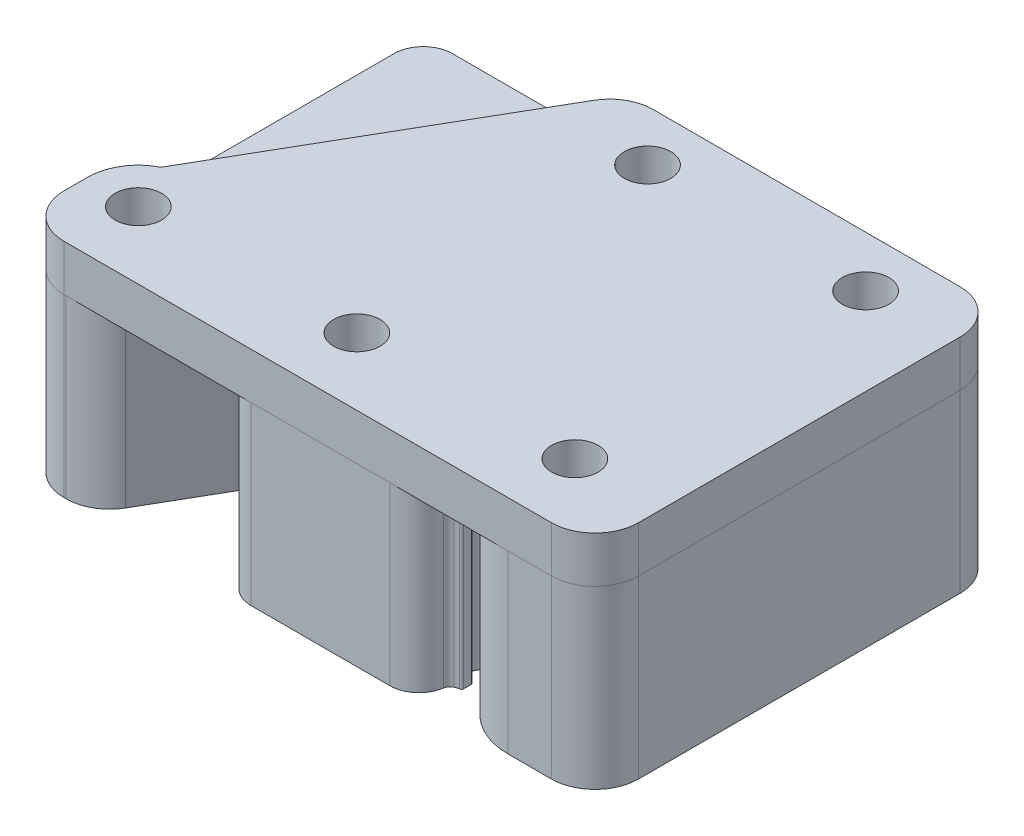
SolidWorks part; units mm, degrees
material "AISI 1045 Steel, cold drawn"
ref_plane "Front Plane" through (0, 0, 0) normal (0, 0, 1) x (1, 0, 0)
ref_plane "Top Plane" through (0, 0, 0) normal (0, 1, 0) x (1, 0, 0)
ref_plane "Right Plane" through (0, 0, 0) normal (1, 0, 0) x (0, 0, -1)
sketch "Sketch1" plane through (0, 0, 0) normal (0, 1, 0) x (1, 0, 0)
  line L0 (-13.5, -13.5) -> (-13.5, -14.619)
  line L1 (7.5, -10) -> (-7.5, -10) construction
  line L2 (7.5, -10) -> (7.5, 10) construction
  line L3 (7.5, 10) -> (-7.5, 10) construction
  line L4 (-7.5, -10) -> (-7.5, 10) construction
  line L5 (7.5, -10) -> (-7.5, 10) construction
  line L6 (7.5, 10) -> (-7.5, -10) construction
  line L7 (13.5, -13.5) -> (-13.5, -13.5) construction
  line L8 (13.5, -13.5) -> (13.5, 13.5)
  line L9 (13.5, 13.5) -> (-13.5, 13.5)
  line L10 (-13.5, -13.5) -> (-13.5, 13.5)
  line L11 (13.5, -13.5) -> (-13.5, 13.5) construction
  line L12 (13.5, 13.5) -> (-13.5, -13.5) construction
  line L13 (-13.5, -14.619) -> (13.5, -14.619)
  line L14 (13.5, -14.619) -> (13.5, -13.5)
  point P0 (0, 0)
  point P6 (0, 0)
  dimension "D1" = 15
  dimension "D2" = 27
  dimension "D3" = 1.119
  dimension "D4" = 20
extrude "Boss-Extrude1" add sketch "Sketch1" along normal mid plane 12.1
hole_wizard "M3 Clearance Hole1" positions "Sketch2" profile "Sketch3" hole size "M3" standard "ANSI Metric" end condition through all
sketch "Sketch2" plane through (0, 6.05, 0) normal (0, 1, 0) x (1, 0, 0)
  point P0 (-7.5, 10)
  point P3 (7.5, 10)
  point P6 (7.5, -10)
  point P9 (-7.5, -10)
sketch "Sketch3" plane through (-7.5, 6.05, -10) normal (1, 0, 0) x (0, 0, 1)
  line L0 (0, 0) -> (0, 12.1)
  line L1 (0, 12.1) -> (1.6, 12.1)
  line L2 (1.6, 12.1) -> (1.6, 0)
  line L5 (1.6, 0) -> (0, 0)
  line L11 (0, -6.35) -> (0, 107.95) construction
  dimension "Thru Hole Dia." = 3.2
  dimension "Thru Hole Depth" = 12.1
sketch "Sketch6" plane through (0, 6.05, 0) normal (0, 1, 0) x (1, 0, 0)
  line L0 (13.5, 13.5) -> (-13.5, 13.5) construction
  line L1 (-13.5, -14.619) -> (-28, -14.619)
  line L2 (-13.5, -14.619) -> (-13.5, 13.5)
  line L3 (-13.5, 13.5) -> (-28, 13.5)
  line L4 (-28, -14.619) -> (-28, 13.5)
  dimension "D1" = 28
extrude "Boss-Extrude3" add sketch "Sketch6" against normal up to surface (12.1 mm away) up to face at (-7.5, -6.05, -8.4)
sketch "Sketch8" plane through (0, 6.05, 0) normal (0, 1, 0) x (1, 0, 0)
  line L0 (-28, -14.619) -> (13.5, -14.619) construction
  line L2 (2.881, -10) -> (2.881, 4)
  line L3 (2.881, 4) -> (1.361, 4)
  line L4 (1.361, -14.619) -> (1.361, 4)
  line L5 (7.5, -14.619) -> (1.361, -14.619)
  arc A0 (2.881, -10) -> (7.5, -14.619) centre (7.5, -10) ccw
  dimension "D1" = 1.52
  dimension "D2" = 14
extrude "Cut-Extrude2" cut sketch "Sketch8" against normal up to surface (12.1 mm away) up to face at (-7.5, -6.05, -8.4)
sketch "Sketch9" plane through (0, 6.05, 0) normal (0, 1, 0) x (1, 0, 0)
  line L1 (2.881, 4) -> (6.306, 4)
  line L2 (2.881, 4) -> (2.881, -8)
  line L3 (2.881, -8) -> (6.306, -8)
  line L4 (6.306, 4) -> (6.306, -8)
  dimension "D1" = 3.425
  dimension "D2" = 12
extrude "Cut-Extrude3" cut sketch "Sketch9" against normal up to surface (12.1 mm away) up to face at (-7.5, -6.05, -8.4)
sketch "Sketch11" plane through (0, 6.05, 0) normal (0, 1, 0) x (1, 0, 0)
  line L1 (2.111, 0.7046) -> (2.111, 4.8734) construction
  line L4 (2.365, -998.8465) -> (2.365, 49001.1535) construction
  line L5 (2.111, 2.2598) -> (2.111, 2)
  line L6 (1.361, 3) -> (2.111, 3) construction
  line L7 (1.361, 4) -> (1.361, -14.619) construction
  line L8 (6.306, 4) -> (1.361, 4) construction
  line L9 (2.111, 2) -> (1.361, 2)
  line L10 (1.361, 2) -> (1.361, 4)
  line L11 (2.111, 4) -> (1.361, 4)
  line L12 (2.111, 3.7402) -> (2.111, 4)
  arc A2 (1.6728, 3.4989) -> (1.6728, 2.5011) centre (1.916, 3) ccw
  arc A4 (1.6728, 2.5011) -> (1.9806, 2.4085) centre (2.111, 3.4) ccw
  arc A5 (2.111, 2.2598) -> (1.9806, 2.4085) centre (1.961, 2.2598) ccw
  arc A6 (2.111, 3.7402) -> (1.9806, 3.5915) centre (1.961, 3.7402) cw
  arc A7 (1.6728, 3.4989) -> (1.9806, 3.5915) centre (2.111, 2.6) cw
  point P7 (1.361, 3)
  line M19 (1.361, -14.619) -> (1.361, 4)
  line M20 (1.361, 4) -> (6.306, 4)
  dimension "D3" = 0.555
  dimension "D4" = 1
  dimension "D5" = 1
  dimension "D6" = 0.15
  dimension "D1" = 0.254
  dimension "D2" = 0.75
  dimension "D7" = 1
extrude "Boss-Extrude4" add sketch "Sketch11" against normal up to surface (12.1 mm away) contours A2 A7 A6 L12 L10 M20 | L5 A5 A4 A2 L9 M19 region at (1.6833, 6.05, -3.7249) region at (1.6833, 6.05, -2.2751) up to face at (-7.5, -6.05, -8.4)
pattern_linear "LPattern1" count 9 spacing 2 along (0, 0, 1) of "Boss-Extrude4"
sketch "Sketch12" plane through (0, 6.05, 0) normal (0, 1, 0) x (1, 0, 0)
  circle A0 centre (2.111, 4) radius 0.5
  circle A1 centre (6.306, 4) radius 0.5
  circle A2 centre (6.306, -8) radius 0.5
  dimension "D1" = 1
extrude "Cut-Extrude5" cut sketch "Sketch12" against normal up to surface (12.1 mm away) up to face at (1.556, -6.05, 5.2005)
sketch "Sketch13" plane through (0, 6.05, 0) normal (0, 1, 0) x (1, 0, 0)
  line L3 (2.111, -14) -> (1.361, -14) construction
  line L4 (2.111, -13.7402) -> (2.111, -14) construction
  line L5 (2.111, -14) -> (1.361, -14)
  line L6 (2.111, -13.7402) -> (2.111, -14)
  line L7 (1.361, -14) -> (1.361, -13)
  arc A6 (1.6728, -12.5011) -> (1.6728, -13.4989) centre (1.916, -13) ccw construction
  arc A7 (1.6728, -13.4989) -> (1.9806, -13.5915) centre (2.111, -12.6) ccw construction
  arc A8 (2.111, -13.7402) -> (1.9806, -13.5915) centre (1.961, -13.7402) ccw construction
  arc A9 (1.361, -13) -> (1.6728, -13.4989) centre (1.916, -13) ccw
  arc A10 (1.6728, -13.4989) -> (1.9806, -13.5915) centre (2.111, -12.6) ccw
  arc A11 (2.111, -13.7402) -> (1.9806, -13.5915) centre (1.961, -13.7402) ccw
extrude "Cut-Extrude6" cut sketch "Sketch13" against normal up to surface (12.1 mm away) up to face at (1.6903, -6.05, 5.2284)
fillet "Fillet3" radius 0.5 7 edges at (5.806, 0, 8) (6.306, 0, 7.5) (5.806, 0, -4) (6.306, 0, -3.5) (2.611, 0, -4) (1.8595, 0, -3.5679) (2.881, 0, 8)
sketch "Sketch17" plane through (0, 6.05, 0) normal (0, 1, 0) x (1, 0, 0)
  line L0 (-21.1595, -14.619) -> (-15.513, -17.879)
  line L11 (-6.4019, 5.9019) -> (-3.8038, 4.4019) construction
  line L12 (-6.4019, 5.9019) -> (-2.9019, 11.9641) construction
  line L13 (-3.8038, 4.4019) -> (-0.3038, 10.4641) construction
  line L14 (-2.9019, 11.9641) -> (-0.3038, 10.4641) construction
  line L15 (-4.201, 12.7141) -> (0.9952, 9.7141) construction
  line L16 (-4.201, 12.7141) -> (-2.701, 15.3122) construction
  line L17 (0.9952, 9.7141) -> (2.4952, 12.3122) construction
  line L18 (-2.701, 15.3122) -> (2.4952, 12.3122) construction
  line L19 (-5.1029, 5.1519) -> (-0.1029, 13.8122) construction
  line L20 (-21.1595, -14.619) -> (-8.5843, 7.1619)
  line L21 (-15.513, -17.879) -> (-2.9378, 3.9019)
  line L22 (-8.5843, 7.1619) -> (-2.9378, 3.9019)
  line L23 (-22.5782, -10.8263) -> (-19.8719, -12.3888) construction
  line L24 (-22.5782, -10.8263) -> (-12.5782, 6.4942) construction
  line L25 (-19.8719, -12.3888) -> (-9.8719, 4.9317) construction
  line L26 (-12.5782, 6.4942) -> (-9.8719, 4.9317) construction
  line L27 (-28, -14.619) -> (1.361, -14.619) construction
  line L28 (-14.8719, -3.7285) -> (-17.5782, -2.166) construction
  circle A0 centre (-7.5, 10) radius 1.6 construction
  circle A1 centre (-7.5, -10) radius 1.6 construction
  dimension "D1" = 6.52
  dimension "D3" = 3
  dimension "D10" = 3
  dimension "D2" = 6
  dimension "D4" = 3
  dimension "D5" = 10
  dimension "D6" = 3.125
  dimension "D7" = 2.5
  dimension "D8" = 60
  dimension "D9" = 3
  dimension "D11" = 20
extrude "Cut-Extrude7" cut sketch "Sketch17" against normal up to surface (12.1 mm away) up to face at (1.9594, -6.05, 4.4571)
sketch "Sketch18" plane through (0, 6.05, 0) normal (0, 1, 0) x (1, 0, 0)
  line L0 (-26.0342, -14.619) -> (-26.0342, -10)
  line L2 (-14.1485, 10.3744) -> (-26.7237, -11.4065)
  line L3 (-12.344, 13.5) -> (-24.1063, -6.8729)
  line L4 (-12.344, 13.5) -> (-28, 13.5)
  line L5 (-28, 13.5) -> (-28, -14.619)
  line L7 (-28, -14.619) -> (-21.1595, -14.619) construction
  line L8 (-8.5843, 7.1619) -> (-21.1595, -14.619) construction
  line L10 (-28, -14.619) -> (-26.0342, -14.619)
  arc A2 (-24.1063, -6.8729) -> (-26.0342, -10) centre (-22.5342, -10) ccw
  point P0 (-7.5, -10)
  dimension "D2" = 3.5
  dimension "D1" = 6.425
extrude "Cut-Extrude8" cut sketch "Sketch18" against normal up to surface (12.1 mm away) contours A2 L10 | A2 L3 L4 L5 L10 region at (-22.8632, 6.05, -4.1187) up to face at (1.2277, -6.05, 4.4618)
hole_wizard "M3 Clearance Hole2" positions "Sketch19" profile "Sketch20" hole size "M3" standard "ANSI Metric" end condition up to next
sketch "Sketch19" plane through (0, 6.05, 0) normal (0, 1, 0) x (1, 0, 0)
  point P0 (-22.5342, -10)
sketch "Sketch20" plane through (-22.5342, 6.05, 10) normal (1, 0, 0) x (0, 0, 1)
  line L0 (0, 0) -> (0, 12.1)
  line L1 (0, 12.1) -> (1.6, 12.1)
  line L2 (1.6, 12.1) -> (1.6, 0)
  line L5 (1.6, 0) -> (0, 0)
  line L11 (0, -6.35) -> (0, 107.95) construction
  dimension "Thru Hole Dia." = 3.2
  dimension "Thru Hole Depth" = 12.1
fillet "Fillet4" radius 3 5 edges at (13.5, 0, 14.619) (13.5, 0, -13.5) (-12.344, 0, -13.5) (-26.0342, 0, 14.619) (-21.1595, 0, 14.619)
sketch "Sketch21" plane through (0, 6.05, 0) normal (0, 1, 0) x (1, 0, 0)
  line L0 (-8.5843, 7.1619) -> (-20.2935, -13.119) construction
  line L1 (-17.8343, -8.8595) -> (-20.8004, -7.147)
  line L2 (-17.8343, -8.8595) -> (-9.3343, 5.8629)
  line L3 (-20.8004, -7.147) -> (-12.3004, 7.5754)
  line L4 (-9.3343, 5.8629) -> (-12.3004, 7.5754)
  line L5 (-2.9378, 3.9019) -> (-8.5843, 7.1619) construction
  dimension "D3" = 17
  dimension "D1" = 3.425
  dimension "D2" = 1.5
extrude "Cut-Extrude9" cut sketch "Sketch21" against normal up to surface (12.1 mm away) up to face at (-22.5342, -6.05, 11.6)
sketch "Sketch22" plane through (0, 6.05, 0) normal (0, 1, 0) x (1, 0, 0)
  circle A0 centre (-20.8004, -7.147) radius 0.5
  circle A1 centre (-12.3004, 7.5754) radius 0.5
  circle A2 centre (-8.5843, 7.1619) radius 0.5
  circle A3 centre (-2.9378, 3.9019) radius 0.5
  arc A4 (2.544, 4.25) -> (1.6303, 3.8625) centre (2.111, 4) ccw construction
extrude "Cut-Extrude10" cut sketch "Sketch22" against normal up to surface (12.1 mm away) up to face at (-22.5342, -6.05, 11.6)
fillet "Fillet5" radius 0.5 10 edges at (-17.8343, 0, 8.8595) (-3.1878, 0, -3.4689) (-3.3708, 0, -4.1519) (-8.8343, 0, -6.7289) (-8.1513, 0, -6.9119) (-11.8674, 0, -7.3254) (-12.5504, 0, -7.1424) (-20.5504, 0, 6.714) (-20.3674, 0, 7.397) (-9.3343, 0, -5.8629)
ref_plane "Plane2" through (6.9551, 0, -12.0466) normal (0.5, 0, -0.866) x (-0.866, 0, -0.5)
sketch "Sketch29" plane through (0, 6.05, 0) normal (0, 1, 0) x (1, 0, 0)
  line L0 (-13.21, 12) -> (-24.1063, -6.8729) construction
  line L1 (-26.0342, -11.619) -> (-26.0342, -10) construction
  line L2 (13.5, -11.619) -> (13.5, 10.5) construction
  line L3 (10.5, 13.5) -> (-10.6119, 13.5) construction
  line L5 (-23.0342, -14.619) -> (10.5, -14.619)
  line L6 (-26.0342, -11.619) -> (-26.0342, -10)
  line L7 (13.5, -11.619) -> (13.5, 10.5)
  line L8 (10.5, 13.5) -> (-10.6119, 13.5)
  line L10 (-13.21, 12) -> (-24.1063, -6.8729)
  arc A0 (-24.1063, -6.8729) -> (-26.0342, -10) centre (-22.5342, -10) ccw construction
  arc A1 (-26.0342, -11.619) -> (-23.0342, -14.619) centre (-23.0342, -11.619) ccw construction
  arc A2 (10.5, -14.619) -> (13.5, -11.619) centre (10.5, -11.619) ccw construction
  arc A3 (13.5, 10.5) -> (10.5, 13.5) centre (10.5, 10.5) ccw construction
  arc A4 (-10.6119, 13.5) -> (-13.21, 12) centre (-10.6119, 10.5) ccw construction
  arc A5 (-24.1063, -6.8729) -> (-26.0342, -10) centre (-22.5342, -10) ccw
  arc A6 (-26.0342, -11.619) -> (-23.0342, -14.619) centre (-23.0342, -11.619) ccw
  arc A7 (10.5, -14.619) -> (13.5, -11.619) centre (10.5, -11.619) ccw
  arc A8 (13.5, 10.5) -> (10.5, 13.5) centre (10.5, 10.5) ccw
  arc A9 (-10.6119, 13.5) -> (-13.21, 12) centre (-10.6119, 10.5) ccw
  circle A12 centre (-22.5342, -10) radius 1.6 construction
  circle A13 centre (-7.5, -10) radius 1.6 construction
  circle A14 centre (7.5, -10) radius 1.6 construction
  circle A15 centre (7.5, 10) radius 1.6 construction
  circle A16 centre (-7.5, 10) radius 1.6 construction
  circle A17 centre (-22.5342, -10) radius 1.6
  circle A18 centre (-7.5, -10) radius 1.6
  circle A19 centre (7.5, -10) radius 1.6
  circle A20 centre (7.5, 10) radius 1.6
  circle A21 centre (-7.5, 10) radius 1.6
extrude "Boss-Extrude7" add sketch "Sketch29" along normal blind 3.175 separate body
hole_wizard "CBORE for M3 SHCS1" positions "Sketch23" profile "Sketch25" counterbore size "M3" standard "ANSI Metric" end condition up to next
sketch "Sketch23" plane through (6.9551, 0, -12.0466) normal (0.5, 0, -0.866) x (-0.866, 0, -0.5)
  line L0 (4.4952, -6.05) -> (9.4952, 6.05) construction
  line L1 (-2.3433, -6.05) -> (15.9402, -6.05) construction
  line L3 (-2.3433, 6.05) -> (15.9402, 6.05) construction
  point P15 (6.9952, 0)
  dimension "D1" = 5
sketch "Sketch25" plane through (0.8971, 0, -15.5442) normal (0, 1, 0) x (-0.866, 0, -0.5)
  line L0 (0, 0) -> (0, 12)
  line L1 (0, 12) -> (1.6, 12)
  line L3 (1.6, 12) -> (1.6, 6)
  line L4 (1.6, 6) -> (3.25, 6)
  line L5 (3.25, 6) -> (3.25, 0)
  line L7 (3.25, 0) -> (0, 0)
  line L11 (0, -6.35) -> (0, 107.95) construction
  dimension "Thru Hole Dia." = 3.2
  dimension "Thru Hole Depth" = 12
  dimension "C'Bore Dia." = 6.5
  dimension "C'Bore Depth" = 6
sketch "Sketch30" plane through (0, 6.05, 0) normal (0, 1, 0) x (1, 0, 0)
  line L1 (3.381, -8) -> (5.44, -8) construction
  line L2 (6.306, -7.134) -> (6.306, 3.134) construction
  line L3 (5.44, 4) -> (2.977, 4) construction
  line L4 (3.381, -8) -> (5.44, -8)
  line L5 (6.306, -7.134) -> (6.306, 3.134)
  line L6 (5.44, 4) -> (2.977, 4)
  line L7 (-18.0843, -9.2926) -> (-9.0843, 6.2959)
  line L8 (-20.0504, -7.5801) -> (-18.2673, -8.6095) construction
  line L9 (-12.7335, 6.8254) -> (-20.3674, -6.397) construction
  line L10 (-9.7673, 6.1129) -> (-11.5504, 7.1424) construction
  line L11 (-20.0504, -7.5801) -> (-18.2673, -8.6095)
  line L12 (-12.7335, 6.8254) -> (-20.3674, -6.397)
  line L13 (-9.7673, 6.1129) -> (-11.5504, 7.1424)
  line L14 (2.881, -8.5) -> (2.881, 4.0093)
  arc A0 (3.381, -8) -> (2.881, -8.5) centre (3.381, -8.5) ccw construction
  arc A1 (5.873, -8.25) -> (5.44, -8) centre (5.44, -8.5) ccw construction
  arc A2 (5.873, -8.25) -> (6.556, -7.567) centre (6.306, -8) ccw construction
  arc A3 (6.306, -7.134) -> (6.556, -7.567) centre (6.806, -7.134) ccw construction
  arc A4 (6.556, 3.567) -> (6.306, 3.134) centre (6.806, 3.134) ccw construction
  arc A5 (6.556, 3.567) -> (5.873, 4.25) centre (6.306, 4) ccw construction
  arc A6 (5.44, 4) -> (5.873, 4.25) centre (5.44, 4.5) ccw construction
  arc A7 (2.544, 4.25) -> (2.977, 4) centre (2.977, 4.5) ccw construction
  arc A8 (3.381, -8) -> (2.881, -8.5) centre (3.381, -8.5) ccw
  arc A9 (5.873, -8.25) -> (5.44, -8) centre (5.44, -8.5) ccw
  arc A10 (5.873, -8.25) -> (6.556, -7.567) centre (6.306, -8) ccw
  arc A11 (6.306, -7.134) -> (6.556, -7.567) centre (6.806, -7.134) ccw
  arc A12 (6.556, 3.567) -> (6.306, 3.134) centre (6.806, 3.134) ccw
  arc A13 (6.556, 3.567) -> (5.873, 4.25) centre (6.306, 4) ccw
  arc A14 (5.44, 4) -> (5.873, 4.25) centre (5.44, 4.5) ccw
  arc A15 (2.881, 4.0093) -> (2.977, 4) centre (2.977, 4.5) ccw
  arc A17 (-18.0843, -9.2926) -> (-18.2673, -8.6095) centre (-18.5173, -9.0426) ccw construction
  arc A18 (-20.0504, -7.5801) -> (-20.5504, -7.5801) centre (-20.3004, -8.0131) ccw construction
  arc A19 (-20.8004, -6.647) -> (-20.3674, -6.397) centre (-20.8004, -6.147) ccw construction
  arc A20 (-12.7335, 6.8254) -> (-12.7335, 7.3254) centre (-13.1665, 7.0754) ccw construction
  arc A21 (-11.8004, 7.5754) -> (-12.7335, 7.3254) centre (-12.3004, 7.5754) ccw construction
  arc A22 (-11.8004, 7.5754) -> (-11.5504, 7.1424) centre (-11.3004, 7.5754) ccw construction
  arc A23 (-9.7673, 6.1129) -> (-9.0843, 6.2959) centre (-9.5173, 6.5459) ccw construction
  arc A24 (-18.0843, -9.2926) -> (-18.2673, -8.6095) centre (-18.5173, -9.0426) ccw
  arc A25 (-20.0504, -7.5801) -> (-20.5504, -7.5801) centre (-20.3004, -8.0131) ccw
  arc A26 (-20.8004, -6.647) -> (-20.3674, -6.397) centre (-20.8004, -6.147) ccw
  arc A27 (-12.7335, 6.8254) -> (-12.7335, 7.3254) centre (-13.1665, 7.0754) ccw
  arc A28 (-11.8004, 7.5754) -> (-12.7335, 7.3254) centre (-12.3004, 7.5754) ccw
  arc A29 (-11.8004, 7.5754) -> (-11.5504, 7.1424) centre (-11.3004, 7.5754) ccw
  arc A30 (-9.7673, 6.1129) -> (-9.0843, 6.2959) centre (-9.5173, 6.5459) ccw
  arc A31 (-20.8004, -6.647) -> (-20.5504, -7.5801) centre (-20.8004, -7.147) ccw construction
  arc A32 (-20.8004, -6.647) -> (-20.5504, -7.5801) centre (-20.8004, -7.147) ccw
extrude "Boss-Extrude8" add sketch "Sketch30" against normal up to surface (12.1 mm away) up to face at (-22.5342, -6.05, 11.6)
fillet "Fillet6" radius 1 1 edges at (2.881, 0, -4.0093)
sketch "Sketch31" plane through (0, 6.05, 0) normal (0, 1, 0) x (1, 0, 0)
  line L0 (13.5, 6.9) -> (4.381, 6.9)
  line L2 (4.381, 6.9) -> (4.381, -6.9)
  line L3 (4.381, -6.9) -> (13.5, -6.9)
  line L4 (2.881, -10) -> (2.881, 3.4759) construction
  line L6 (13.5, 6.9) -> (13.5, -6.9)
  line L7 (13.5, -11.619) -> (13.5, 10.5) construction
  circle A0 centre (7.5, -10) radius 1.6 construction
  circle A1 centre (7.5, 10) radius 1.6 construction
  dimension "D1" = 3.1
  dimension "D2" = 3.1
  dimension "D3" = 1.5
extrude "Cut-Extrude11" cut sketch "Sketch31" against normal up to surface (12.1 mm away) up to face at (-0.8329, -6.05, 3.7569)
sketch "Sketch32" plane through (0, 6.05, 0) normal (0, 1, 0) x (1, 0, 0)
  line L0 (-10.0574, 7.6105) -> (-19.366, -8.5125)
  line L1 (-9.0173, 6.4119) -> (-20.2935, -13.119) construction
  line L2 (-13.21, 12) -> (-24.1063, -6.8729) construction
  line L3 (-13.21, 12) -> (-24.1063, -6.8729)
  line L5 (10.5, 13.5) -> (-10.6119, 13.5) construction
  line L6 (-7.5, 13.5) -> (-10.6119, 13.5)
  arc A0 (-19.366, -8.5125) -> (-24.1063, -6.8729) centre (-22.5342, -10) ccw
  arc A1 (-24.1063, -6.8729) -> (-26.0342, -10) centre (-22.5342, -10) ccw construction
  arc A2 (-7.5, 13.5) -> (-10.0574, 7.6105) centre (-7.5, 10) ccw
  arc A3 (-10.6119, 13.5) -> (-13.21, 12) centre (-10.6119, 10.5) ccw construction
  arc A4 (-10.6119, 13.5) -> (-13.21, 12) centre (-10.6119, 10.5) ccw
  dimension "D1" = 1.5
extrude "Cut-Extrude12" cut sketch "Sketch32" against normal up to surface (12.1 mm away) up to face at (-0.3561, -6.05, 3.5736)
sketch "Sketch34" plane through (0, -6.05, 0) normal (0, -1, 0) x (1, 0, 0)
  line L0 (0.111, -6.1826) -> (-7.4426, 6.9005)
  line L1 (-3.3708, -3.1519) -> (-13.6309, 14.619) construction
  line L2 (0.111, -6.1826) -> (0.111, 12.619)
  line L4 (0.111, 12.619) -> (-5.8414, 12.619)
  line L5 (2.111, 10.2598) -> (2.111, 9.7402) construction
  line L7 (-13.6309, 14.619) -> (1.361, 14.619) construction
  circle A2 centre (-7.5, 10) radius 3.1
  arc A3 (-7.4426, 6.9005) -> (-5.8414, 12.619) centre (-7.5, 10) ccw
  dimension "D2" = 1.5
  dimension "D3" = 2
  dimension "D4" = 2
  dimension "D1" = 1.5
extrude "Cut-Extrude14" cut sketch "Sketch34" against normal up to surface (12.1 mm away) up to face at (-0.2449, 6.05, 3.6119)
sketch "Sketch35" plane through (0, -6.05, 0) normal (0, -1, 0) x (1, 0, 0)
  line L0 (-4.9175, -11.9731) -> (0.7117, -8.7231) construction
  line L1 (-7.5622, -13.5) -> (1.2713, -8.4)
  line L2 (10.5, -13.5) -> (-7.5, -13.5) construction
  line L3 (1.2713, -8.4) -> (4.3871, -8.4)
  line L4 (7.5, -13.5) -> (-7.5622, -13.5)
  line L6 (4.381, -6.9) -> (13.5, -6.9) construction
  circle A1 centre (7.5, -10) radius 1.6 construction
  arc A3 (4.3871, -8.4) -> (7.5, -13.5) centre (7.5, -10) ccw
  dimension "D1" = 1.5
extrude "Cut-Extrude15" cut sketch "Sketch35" against normal up to surface (12.1 mm away) up to face at (-2.7337, 6.05, 6.3401)
fillet "Fillet7" radius 2 9 edges at (-13.6309, 0, 14.619) (1.361, 0, 14.619) (13.5, 0, 6.9) (4.381, 0, 6.9) (13.5, 0, -6.9) (4.381, 0, -6.9) (-19.366, 0, 8.5125) (-7.5612, 0, -13.4995) (-10.0574, 0, -7.6105)
fillet "Fillet8" radius 1 6 edges at (0.111, 0, 12.619) (0.111, 0, -6.1826) (-5.8414, 0, 12.619) (-7.4426, 0, 6.9005) (4.3871, 0, -8.4) (1.2713, 0, -8.4)
sketch "Sketch36" plane through (0, 6.05, 0) normal (0, 1, 0) x (1, 0, 0)
  line L0 (2.881, 4.4759) -> (2.881, 3.4759)
  line L1 (1.611, 4) -> (1.611, 4.4759)
  arc A0 (1.611, 4.4759) -> (2.881, 4.4759) centre (2.246, 4.4759) cw
  arc A3 (2.544, 4.25) -> (1.6303, 3.8625) centre (2.111, 4) ccw construction
  arc A4 (2.544, 4.25) -> (2.6117, 4.1586) centre (2.977, 4.5) ccw construction
  arc A5 (2.881, 3.4759) -> (2.6117, 4.1586) centre (1.881, 3.4759) ccw construction
  arc A6 (2.544, 4.25) -> (1.611, 4) centre (2.111, 4) ccw
  arc A7 (2.544, 4.25) -> (2.6117, 4.1586) centre (2.977, 4.5) ccw
  arc A8 (2.881, 3.4759) -> (2.6117, 4.1586) centre (1.881, 3.4759) ccw
  dimension "D1" = 1
extrude "Cut-Extrude16" cut sketch "Sketch36" against normal up to surface (12.1 mm away) up to face at (-2.9137, -6.05, 6.8822)
sketch "Sketch37" plane through (0, 6.05, 0) normal (0, 1, 0) x (1, 0, 0)
  line L0 (-10.6817, 6.5291) -> (-9.847, 7.9748)
  line L1 (-18.0522, -6.2369) -> (-10.6817, 6.5291) construction
  line L2 (1.0392, 8.534) -> (-6.9682, 13.1571) construction
  line L3 (-6.6764, 12.9886) -> (-6.9682, 13.1571)
  arc A0 (-6.6764, 12.9886) -> (-9.847, 7.9748) centre (-7.5, 10) ccw
  circle A1 centre (-7.5, 10) radius 1.6 construction
  arc A2 (-6.9682, 13.1571) -> (-8.5926, 13.3251) centre (-7.9682, 11.425) ccw construction
  arc A3 (-8.5926, 13.3251) -> (-10.6269, 8.4276) centre (-7.5, 10) ccw construction
  arc A4 (-10.6817, 6.5291) -> (-10.6269, 8.4276) centre (-12.4137, 7.5291) ccw construction
  arc A5 (-6.9682, 13.1571) -> (-8.5926, 13.3251) centre (-7.9682, 11.425) ccw
  arc A6 (-8.5926, 13.3251) -> (-10.6269, 8.4276) centre (-7.5, 10) ccw
  arc A7 (-10.6817, 6.5291) -> (-10.6269, 8.4276) centre (-12.4137, 7.5291) ccw
  dimension "D1" = 1.5
extrude "Cut-Extrude17" cut sketch "Sketch37" against normal up to surface (12.1 mm away) up to face at (-2.9137, -6.05, 6.8822)
fillet "Fillet9" radius 2 2 edges at (-6.6764, 0, -12.9886) (-9.847, 0, -7.9748)
sketch "Sketch38" plane through (0, 6.05, 0) normal (0, 1, 0) x (1, 0, 0)
  line L0 (-26.0342, -10) -> (-26.0342, 13.1)
  line L1 (-26.0342, 13.1) -> (-7.5, 13.1)
  line L2 (-24.5342, -7.1277) -> (-24.5342, 11.6)
  line L3 (-24.5342, 11.6) -> (-10.1552, 11.6)
  line L4 (-24.5342, -10) -> (-24.5342, 11.6) construction
  line L5 (-24.5342, 11.6) -> (-7.5, 11.6) construction
  arc A0 (-7.2093, 13.0863) -> (-10.3388, 8.7545) centre (-7.5, 10) ccw construction
  arc A1 (-7.5, 13.1) -> (-10.1552, 11.6) centre (-7.5, 10) ccw
  arc A2 (-20.7842, -6.9689) -> (-26.0342, -10) centre (-22.5342, -10) ccw construction
  arc A3 (-24.5342, -7.1277) -> (-26.0342, -10) centre (-22.5342, -10) ccw
  dimension "D1" = 1.5
extrude "Boss-Extrude9" add sketch "Sketch38" against normal up to surface (12.1 mm away) up to face at (-2.9137, -6.05, 6.8822)
fillet "Fillet10" radius 2 4 edges at (-24.5342, 0, 7.1277) (-10.1552, 0, -11.6) (-26.0342, 0, -13.1) (-24.5342, 0, -11.6)
sketch "Sketch39" plane through (0.9551, 0, -1.6543) normal (-0.5, 0, 0.866) x (0.866, 0, 0.5)
  circle A0 centre (-6.9952, 0) radius 1.6 construction
  circle A1 centre (-6.9952, 0) radius 1.6
extrude "Boss-Extrude10" add sketch "Sketch39" against normal up to surface (6 mm away)
sketch "Sketch40" plane through (0, 6.05, 0) normal (0, 1, 0) x (1, 0, 0)
  line L0 (-22.5342, 11.6) -> (-12.5843, 11.6) construction
  line L1 (-24.5342, -4.5) -> (-24.5342, 9.6) construction
  line L2 (-18.0522, -6.2369) -> (-10.4382, 6.9509) construction
  line L3 (-22.5342, 11.6) -> (-12.5843, 11.6)
  line L4 (-24.5342, -4.5) -> (-24.5342, 9.6)
  line L5 (-18.0522, -6.2369) -> (-10.4382, 6.9509)
  line L6 (0.111, 2.4506) -> (0.111, -11.619) construction
  line L7 (-0.889, -12.619) -> (-3.7332, -12.619) construction
  line L8 (-6.7643, -5.7258) -> (-1.755, 2.9506) construction
  line L9 (0.111, 2.4506) -> (0.111, -11.619)
  line L10 (-0.889, -12.619) -> (-3.7332, -12.619)
  line L11 (-6.7643, -5.7258) -> (-1.755, 2.9506)
  line L12 (6.381, -6.9) -> (11.5, -6.9) construction
  line L13 (4.381, 4.9) -> (4.381, -4.9) construction
  line L14 (11.5, 6.9) -> (6.381, 6.9) construction
  line L15 (6.381, -6.9) -> (11.5, -6.9)
  line L16 (4.381, 4.9) -> (4.381, -4.9)
  line L17 (11.5, 6.9) -> (6.381, 6.9)
  line L18 (13.5, 8.9) -> (13.5, -8.9)
  arc A0 (-10.4382, 6.9509) -> (-10.3388, 8.7545) centre (-12.1702, 7.9509) ccw construction
  arc A1 (-10.5905, 9.7569) -> (-10.3388, 8.7545) centre (-7.5, 10) ccw construction
  arc A2 (-10.5905, 9.7569) -> (-12.5843, 11.6) centre (-12.5843, 9.6) ccw construction
  arc A3 (-22.5342, 11.6) -> (-24.5342, 9.6) centre (-22.5342, 9.6) ccw construction
  arc A4 (-24.5342, -4.5) -> (-22.5342, -6.5) centre (-22.5342, -4.5) ccw construction
  arc A5 (-20.7842, -6.9689) -> (-22.5342, -6.5) centre (-22.5342, -10) ccw construction
  arc A6 (-20.7842, -6.9689) -> (-18.0522, -6.2369) centre (-19.7842, -5.2369) ccw construction
  arc A7 (-10.4382, 6.9509) -> (-10.3388, 8.7545) centre (-12.1702, 7.9509) ccw
  arc A8 (-10.5905, 9.7569) -> (-10.3388, 8.7545) centre (-7.5, 10) ccw
  arc A9 (-10.5905, 9.7569) -> (-12.5843, 11.6) centre (-12.5843, 9.6) ccw
  arc A10 (-22.5342, 11.6) -> (-24.5342, 9.6) centre (-22.5342, 9.6) ccw
  arc A11 (-24.5342, -4.5) -> (-22.5342, -6.5) centre (-22.5342, -4.5) ccw
  arc A12 (-20.7842, -6.9689) -> (-22.5342, -6.5) centre (-22.5342, -10) ccw
  arc A13 (-20.7842, -6.9689) -> (-18.0522, -6.2369) centre (-19.7842, -5.2369) ccw
  arc A14 (0.111, 2.4506) -> (-1.755, 2.9506) centre (-0.889, 2.4506) ccw construction
  arc A15 (-0.889, -12.619) -> (0.111, -11.619) centre (-0.889, -11.619) ccw construction
  arc A16 (-4.6519, -11.2241) -> (-3.7332, -12.619) centre (-3.7332, -11.619) ccw construction
  arc A17 (-4.6519, -11.2241) -> (-6.289, -7.1463) centre (-7.5, -10) ccw construction
  arc A18 (-6.7643, -5.7258) -> (-6.289, -7.1463) centre (-5.8983, -6.2258) ccw construction
  arc A19 (0.111, 2.4506) -> (-1.755, 2.9506) centre (-0.889, 2.4506) ccw
  arc A20 (-0.889, -12.619) -> (0.111, -11.619) centre (-0.889, -11.619) ccw
  arc A21 (-4.6519, -11.2241) -> (-3.7332, -12.619) centre (-3.7332, -11.619) ccw
  arc A22 (-4.6519, -11.2241) -> (-6.289, -7.1463) centre (-7.5, -10) ccw
  arc A23 (-6.7643, -5.7258) -> (-6.289, -7.1463) centre (-5.8983, -6.2258) ccw
  arc A24 (13.5, -8.9) -> (11.5, -6.9) centre (11.5, -8.9) ccw construction
  arc A25 (4.381, -4.9) -> (6.381, -6.9) centre (6.381, -4.9) ccw construction
  arc A26 (6.381, 6.9) -> (4.381, 4.9) centre (6.381, 4.9) ccw construction
  arc A27 (11.5, 6.9) -> (13.5, 8.9) centre (11.5, 8.9) ccw construction
  arc A28 (13.5, -8.9) -> (11.5, -6.9) centre (11.5, -8.9) ccw
  arc A29 (4.381, -4.9) -> (6.381, -6.9) centre (6.381, -4.9) ccw
  arc A30 (6.381, 6.9) -> (4.381, 4.9) centre (6.381, 4.9) ccw
  arc A31 (11.5, 6.9) -> (13.5, 8.9) centre (11.5, 8.9) ccw
extrude "Boss-Extrude11" add sketch "Sketch40" against normal up to surface (12.1 mm away) up to face at (-17.7037, -6.05, -3.3974)
